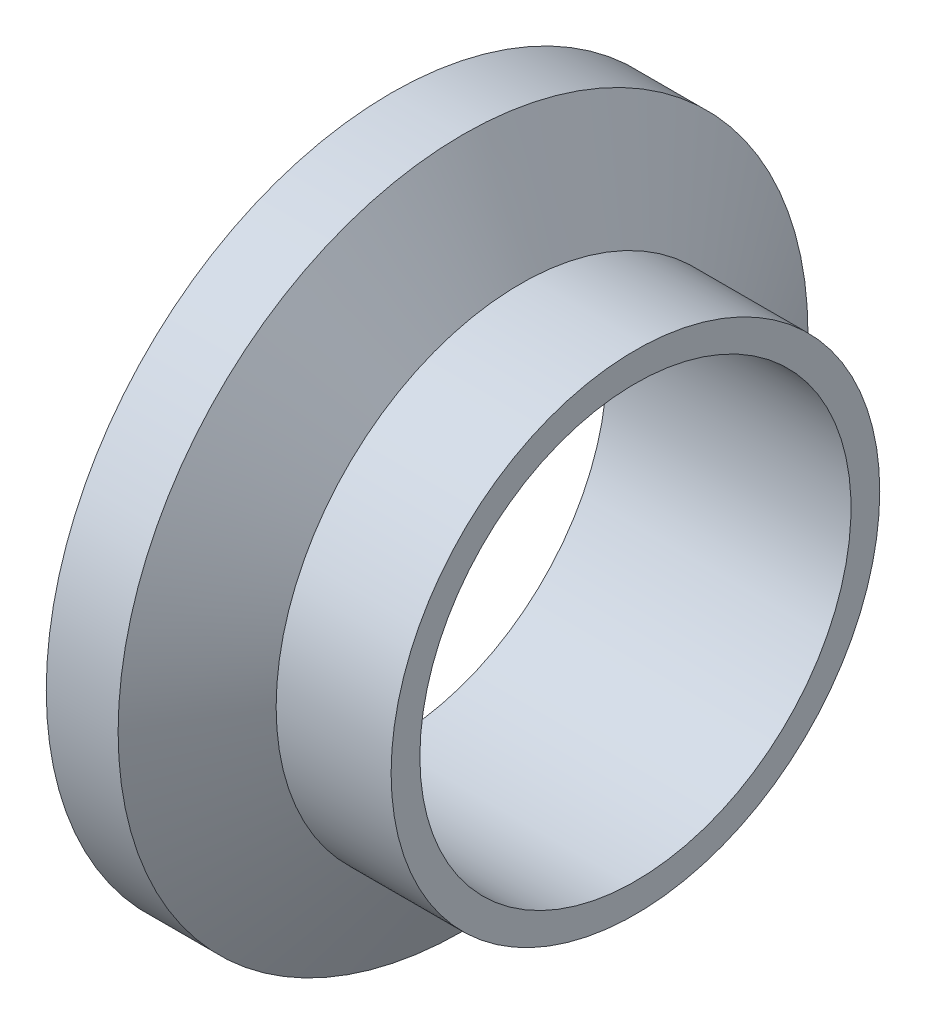
SolidWorks part; units mm, degrees
material "Stop 1060"
ref_plane "Plano frontal" through (0, 0, 0) normal (0, 0, 1) x (1, 0, 0)
ref_plane "Plano superior" through (0, 0, 0) normal (0, 1, 0) x (1, 0, 0)
ref_plane "Plano direito" through (0, 0, 0) normal (1, 0, 0) x (0, 0, -1)
sketch "Esboço1" plane through (0, 0, 0) normal (0, 0, 1) x (1, 0, 0)
  line L0 (-8.5, 0) -> (8.5, 0) construction
  line L1 (-8.5, 24) -> (-8.5, 15)
  line L2 (-8.5, 24) -> (-3.5, 24)
  line L3 (-3.5, 24) -> (0.4952, 17)
  line L4 (0.4952, 17) -> (8.4952, 17)
  line L5 (8.4952, 17) -> (8.4952, 15)
  line L6 (8.4952, 15) -> (-8.5, 15)
  dimension "D1" = 17
  dimension "D2" = 2
  dimension "D3" = 9
  dimension "D4" = 8
  dimension "D6" = 15
revolve "Revolução1" add sketch "Esboço1" angle 360 about L0
